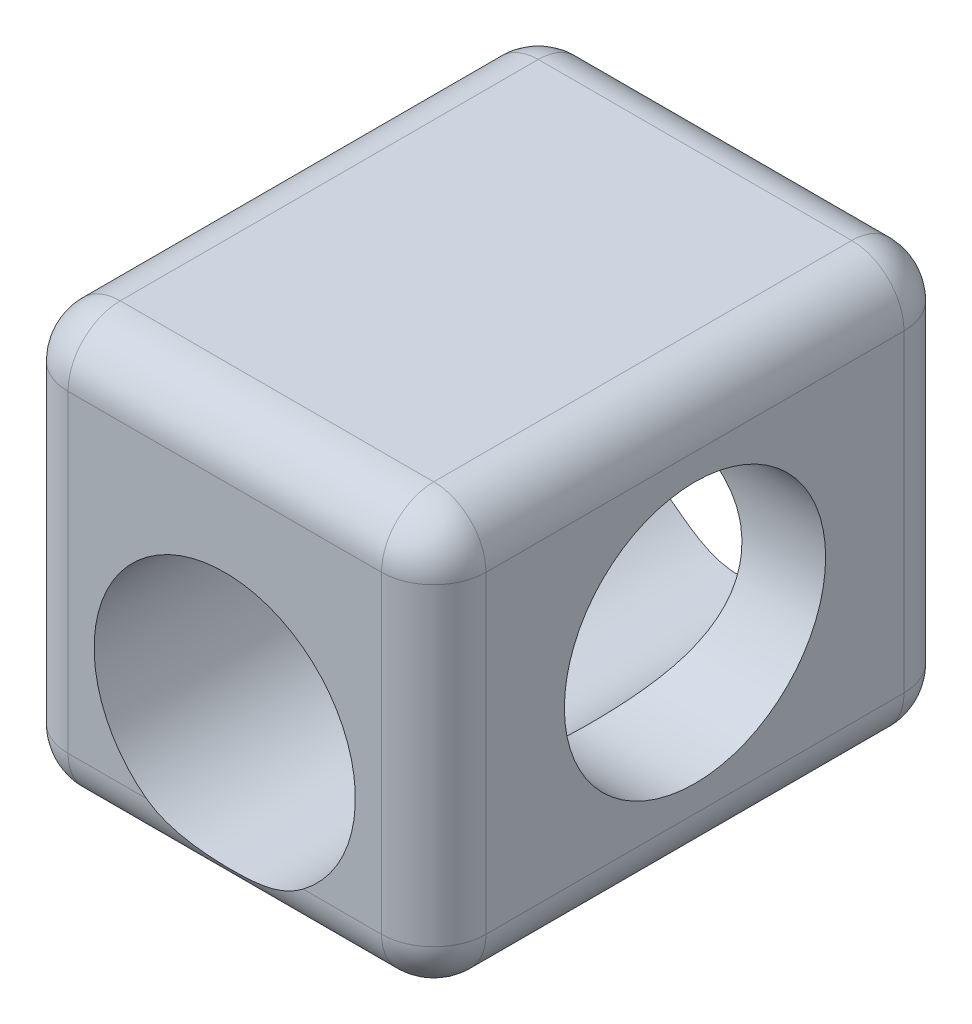
SolidWorks part; units mm, degrees
material "ABS"
ref_plane "前视基准面" through (0, 0, 0) normal (0, 0, 1) x (1, 0, 0)
ref_plane "上视基准面" through (0, 0, 0) normal (0, 1, 0) x (1, 0, 0)
ref_plane "右视基准面" through (0, 0, 0) normal (1, 0, 0) x (0, 0, -1)
other "Configuration Table"
sketch "草图1" plane through (0, 0, 0) normal (0, 0, 1) x (1, 0, 0)
  line L1 (0, 8) -> (8, 8)
  line L2 (0, 8) -> (0, 0)
  line L3 (0, 0) -> (8, 0)
  line L4 (8, 8) -> (8, 0)
  dimension "D1" = 8
  dimension "D2" = 8
extrude "凸台-拉伸1" add sketch "草图1" along normal blind 10
sketch "草图2" plane through (0, 0, 10) normal (0, 0, 1) x (1, 0, 0)
  line L0 (0, 0) -> (8, 0) construction
  line L1 (0, 8) -> (0, 0) construction
  circle A0 centre (4, 3) radius 2.5
  dimension "D1" = 3
  dimension "D2" = 4
  dimension "D3" = 5
extrude "切除-拉伸1" cut sketch "草图2" against normal through all
sketch "草图4" plane through (8, 0, 0) normal (1, 0, 0) x (0, 0, -1)
  line L0 (-10, 4) -> (0, 4) construction
  line L1 (-10, 0) -> (-10, 8) construction
  line L2 (0, 0) -> (0, 8) construction
  circle A0 centre (-5, 4) radius 2.5
  dimension "D1" = 5
  dimension "D2" = 5
extrude "切除-拉伸2" cut sketch "草图4" against normal through all
fillet "圆角1" radius 1 12 edges at (0, 0, 5) (4, 0, 10) (8, 0, 5) (4, 0, 0) (8, 8, 5) (4, 8, 10) (0, 8, 5) (4, 8, 0) (0, 4, 0) (0, 4, 10) (8, 4, 10) (8, 4, 0)
